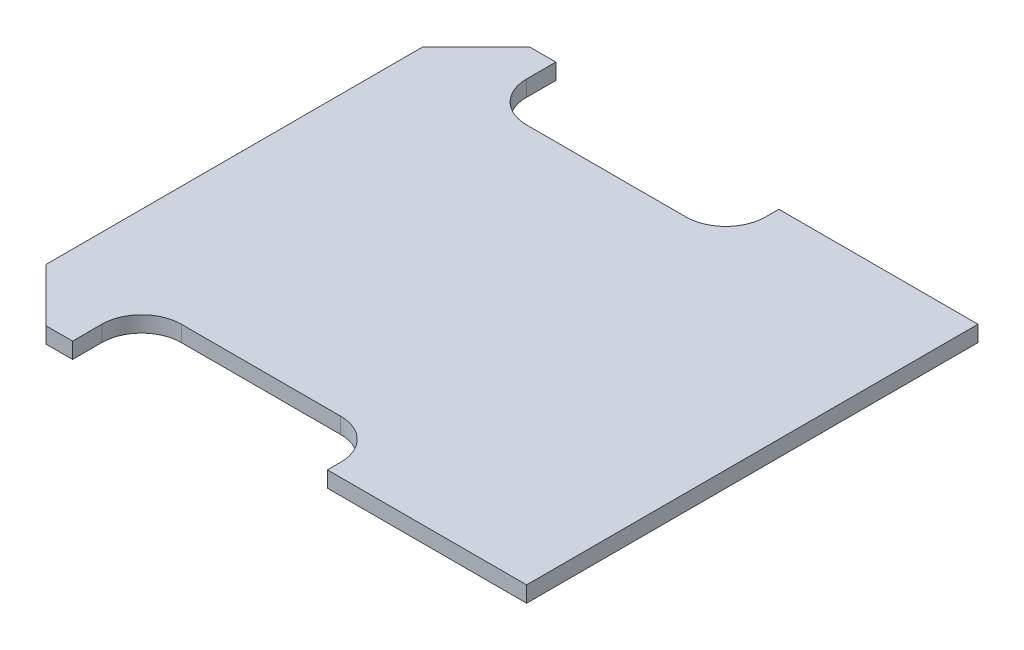
SolidWorks part; units mm, degrees
material "ABS"
ref_plane "Front Plane" through (0, 0, 0) normal (0, 0, 1) x (1, 0, 0)
ref_plane "Top Plane" through (0, 0, 0) normal (0, 1, 0) x (1, 0, 0)
ref_plane "Right Plane" through (0, 0, 0) normal (1, 0, 0) x (0, 0, -1)
sketch "Sketch1" plane through (0, 0, 0) normal (0, 1, 0) x (1, 0, 0)
  line L1 (-97.5, 85) -> (97.5, 85)
  line L2 (-97.5, 85) -> (-97.5, -85)
  line L3 (-97.5, -85) -> (97.5, -85)
  line L4 (97.5, 85) -> (97.5, -85)
  line L5 (-97.5, 85) -> (97.5, -85) construction
  line L6 (-97.5, -85) -> (97.5, 85) construction
  point P0 (0, 0)
  dimension "D1" = 195
  dimension "D2" = 170
extrude "Boss-Extrude1" add sketch "Sketch1" along normal blind 6
sketch "Sketch2" plane through (0, 6, 0) normal (0, 1, 0) x (1, 0, 0)
  line L0 (-97.5, -85) -> (-67.5, -85) construction
  line L1 (-97.5, -85) -> (97.5, -85) construction
  line L2 (0, 0) -> (-97.5, 0) construction
  line L3 (-67.5, -85) -> (22.5, -85)
  line L4 (-67.5, -85) -> (-67.5, -65)
  line L5 (-67.5, -65) -> (22.5, -65)
  line L6 (22.5, -85) -> (22.5, -65)
  line L7 (-97.5, 85) -> (-97.5, -85) construction
  line L8 (-67.5, 65) -> (22.5, 65)
  line L9 (22.5, 85) -> (22.5, 65)
  line L10 (-67.5, 85) -> (22.5, 85)
  line L11 (-67.5, 85) -> (-67.5, 65)
  dimension "D1" = 30
  dimension "D2" = 90
  dimension "D3" = 20
extrude "Cut-Extrude1" cut sketch "Sketch2" against normal through all
fillet "Fillet1" radius 15 4 edges at (22.5, 3, -65) (-67.5, 3, -65) (-67.5, 3, 65) (22.5, 3, 65)
sketch "Sketch3" plane through (0, 6, 0) normal (0, 1, 0) x (1, 0, 0)
  line L0 (0, 0) -> (-97.5, 0) construction
  line L1 (-67.5, 85) -> (-97.5, 85)
  line L2 (-67.5, 85) -> (-67.5, 91)
  line L3 (-67.5, 91) -> (-97.5, 91)
  line L4 (-97.5, 85) -> (-97.5, 91)
  line L5 (-97.5, 85) -> (-97.5, -85) construction
  line L6 (-67.5, -91) -> (-97.5, -91)
  line L7 (-97.5, -85) -> (-97.5, -91)
  line L8 (-67.5, -85) -> (-97.5, -85)
  line L9 (-67.5, -85) -> (-67.5, -91)
  dimension "D1" = 6
extrude "Boss-Extrude2" add sketch "Sketch3" against normal up to surface (6 mm away) up to face at (-16.875, 0, 0)
chamfer "Chamfer1" distance 20 angle 45 2 edges at (-97.5, 3, -91) (-97.5, 3, 91)
sketch "Sketch4" plane through (0, 0, 0) normal (0, -1, 0) x (1, 0, 0)
  line L0 (51.5, -75) -> (82.1667, -75) construction
  line L1 (143.5, -85) -> (51.5, -85) construction
  line L2 (143.5, -85) -> (143.5, -65) construction
  line L3 (143.5, -65) -> (51.5, -65) construction
  line L4 (51.5, -85) -> (51.5, -65) construction
  line L5 (82.1667, -75) -> (112.8333, -75) construction
  line L6 (-77.5, -91) -> (-67.5, -91) construction
  line L7 (-67.5, -91) -> (-67.5, -80) construction
  line L9 (97.5, -85) -> (22.5, -85) construction
  line L10 (112.8333, -75) -> (143.5, -75) construction
  line L11 (97.5, 85) -> (97.5, -85) construction
  line L12 (0, 0) -> (97.5, 0) construction
  circle A0 centre (82.1667, -75) radius 6.1
  circle A1 centre (82.1667, 75) radius 6.1
  circle A2 centre (-75.5, -79.6) radius 6.1
  circle A3 centre (-75.5, 79.6) radius 6.1
  point P7 (97.5, -75)
  dimension "D3" = 12.2
  dimension "D6" = 12.2
  dimension "D1" = 92
  dimension "D2" = 20
  dimension "D4" = 11.4
  dimension "D5" = 8
extrude "Cut-Extrude2" cut sketch "Sketch4" against normal blind 3.2
fillet "Fillet2" radius 0.2 4 edges at (82.1667, 0, 81.1) (82.1667, 0, -81.1) (-75.5, 0, 85.7) (-75.5, 0, -85.7)
